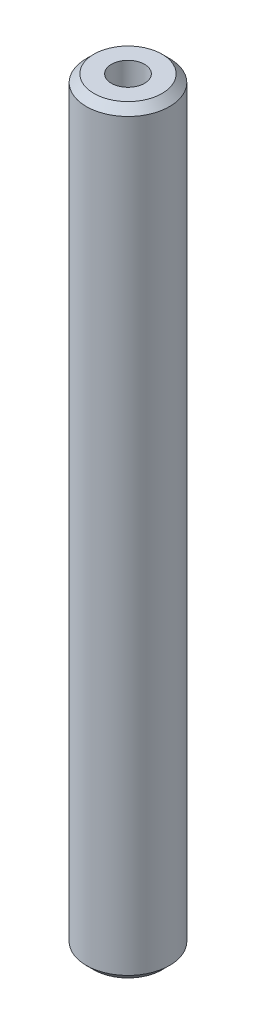
SolidWorks part; units mm, degrees
ref_plane "Front Plane" through (0, 0, 0) normal (0, 0, 1) x (1, 0, 0)
ref_plane "Top Plane" through (0, 0, 0) normal (0, 1, 0) x (1, 0, 0)
ref_plane "Right Plane" through (0, 0, 0) normal (1, 0, 0) x (0, 0, -1)
sketch "Sketch1" plane through (0, 0, 0) normal (0, 1, 0) x (1, 0, 0)
  circle A0 centre (0, 0) radius 15
  dimension "SHAFT_OD" = 30
extrude "Boss-Extrude1" add sketch "Sketch1" along normal blind 273.531
sketch "Sketch2" plane through (0, 0, 0) normal (0, 1, 0) x (1, 0, 0)
  circle A0 centre (0, 0) radius 5.9628
  dimension "BORE_D" = 11.9257
extrude "Cut-Extrude1" cut sketch "Sketch2" along normal through all
chamfer "Chamfer1" distance 2.7242 angle 45 2 edges at (0, 273.531, 15) (0, 0, 15)
